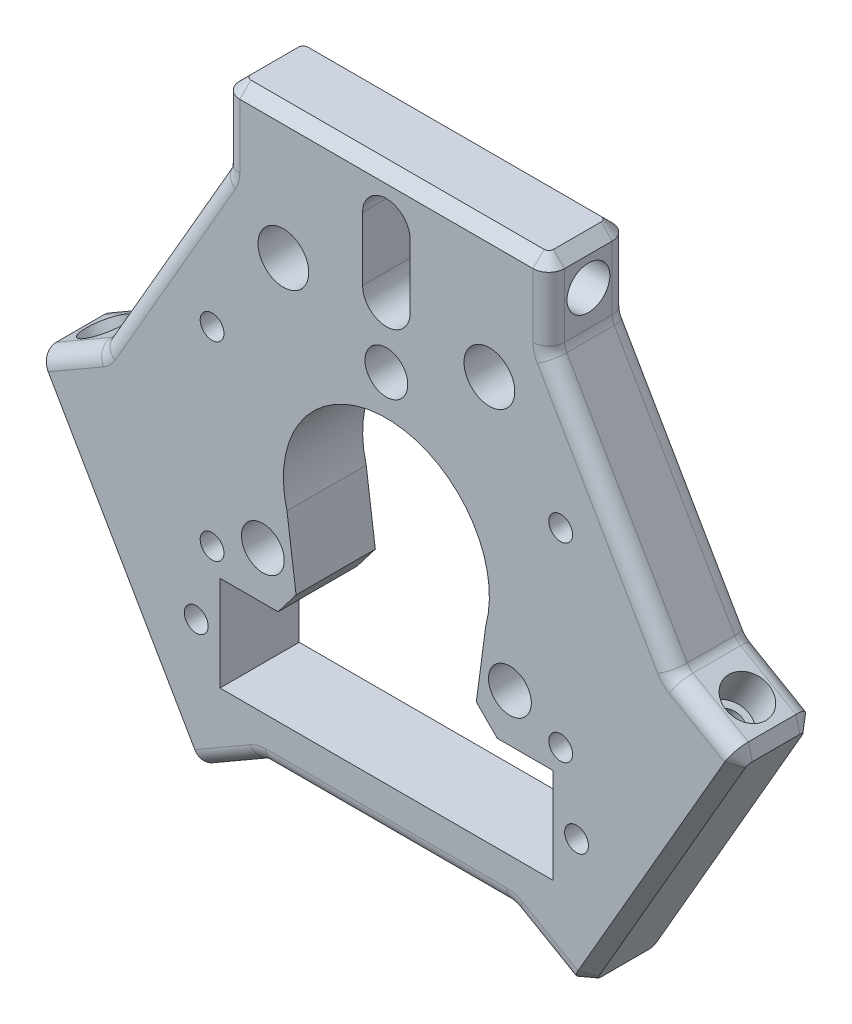
SolidWorks part; units mm, degrees
ref_plane "前基準面" through (0, 0, 0) normal (0, 0, 1) x (1, 0, 0)
ref_plane "上基準面" through (0, 0, 0) normal (0, 1, 0) x (1, 0, 0)
ref_plane "右基準面" through (0, 0, 0) normal (1, 0, 0) x (0, 0, -1)
sketch "草圖1" plane through (0, 0, 0) normal (0, 0, 1) x (1, 0, 0)
  line L0 (0, 0) -> (0, 40) construction
  line L1 (-20.5, 40) -> (20.5, 40)
  line L2 (20.5, 40) -> (20.5, 30)
  line L3 (-20.5, 40) -> (-20.5, 30)
  line L4 (44.891, -2.2465) -> (36.2308, 2.7535)
  line L5 (44.891, -2.2465) -> (24.391, -37.7535)
  line L6 (24.391, -37.7535) -> (15.7308, -32.7535)
  line L7 (-24.391, -37.7535) -> (-15.7308, -32.7535)
  line L8 (-24.391, -37.7535) -> (-44.891, -2.2465)
  line L9 (-44.891, -2.2465) -> (-36.2308, 2.7535)
  line L10 (-36.2308, 2.7535) -> (-20.5, 30)
  line L11 (20.5, 30) -> (36.2308, 2.7535)
  line L12 (15.7308, -32.7535) -> (-15.7308, -32.7535)
  line L13 (0, 0) -> (34.641, -20) construction
  line L14 (0, 0) -> (-34.641, -20) construction
  circle A0 centre (0, 0) radius 13
  point P6 (0, 0)
  point P9 (0, 40)
  point P22 (0, 0)
  point P23 (0, 0)
  dimension "D1" = 26
  dimension "D2" = 40
  dimension "D3" = 20.5
  dimension "D4" = 10
  dimension "D6" = 20.5
  dimension "D7" = 3
  dimension "D8" = 40
  dimension "D9" = 40
  dimension "D10" = 72.7535
  dimension "D5" = 3
extrude "填料-伸長1" add sketch "草圖1" along normal blind 10
ref_plane "平面1" through (0, 4.6791, 12.8558) normal (0, 0.342, 0.9397) x (-1, 0, 0)
sketch "草圖2" plane through (-20.5, 0, 0) normal (-1, 0, 0) x (0, 0, 1)
  circle A0 centre (5, 35) radius 2.7
  dimension "D1" = 5.4
extrude "除料-伸長1" cut sketch "草圖2" against normal blind 5
mirror "鏡射1" about plane through (0, 0, 0) normal (1, 0, 0) of "除料-伸長1"
pattern_circular "環狀複製排列1" count 3 over 360 about axis through (0, 0, 10) along (0, 0, -1) of "除料-伸長1", "鏡射1"
sketch "草圖3" plane through (0, 0, 10) normal (0, 0, -1) x (-1, 0, 0)
  circle A0 centre (0, 18) radius 2.7
  circle A1 centre (15.5885, -9) radius 2.7
  circle A2 centre (-15.5885, -9) radius 2.7
  point P8 (0, 0)
  dimension "D1" = 5.4
  dimension "D3" = 18
  dimension "D2" = 3
extrude "除料-伸長2" cut sketch "草圖3" along normal blind 5
sketch "草圖4" plane through (0, 0, 0) normal (0, 0, -1) x (-1, 0, 0)
  line L0 (0, -32.7535) -> (0, 40) construction
  line L1 (15.7308, -32.7535) -> (-15.7308, -32.7535) construction
  line L2 (-63.2298, 0) -> (49.6692, 0) construction
  line L3 (-20.5, 40) -> (20.5, 40) construction
  circle A1 centre (22, -12) radius 1.5
  circle A2 centre (22, 12) radius 1.5
  circle A3 centre (-22, 12) radius 1.5
  circle A4 centre (-22, -12) radius 1.5
  dimension "D3" = 3
  dimension "D4" = 3
  dimension "D1" = 24
  dimension "D2" = 12
  dimension "D5" = 22
extrude "除料-伸長3" cut sketch "草圖4" against normal through all
sketch "草圖6" plane through (0, 0, 10) normal (0, 0, 1) x (1, 0, 0)
  line L0 (0, 34) -> (0, 26) construction
  line L1 (3, 34) -> (3, 26)
  line L2 (-3, 34) -> (-3, 26)
  arc A0 (3, 34) -> (-3, 34) centre (0, 34) ccw
  arc A1 (-3, 26) -> (3, 26) centre (0, 26) ccw
  point P4 (0, 30)
  dimension "D1" = 8
  dimension "D2" = 6
  dimension "D3" = 26
extrude "除料-伸長5" cut sketch "草圖6" against normal through all
sketch "草圖7" plane through (0, 0, 10) normal (0, 0, 1) x (1, 0, 0)
  line L0 (0, 0) -> (0, -32.7535) construction
  line L1 (-15.7308, -32.7535) -> (15.7308, -32.7535) construction
  circle A0 centre (-13, 24) radius 3.2
  circle A1 centre (13, 24) radius 3.2
  dimension "D1" = 6.4
  dimension "D2" = 13
  dimension "D3" = 24
extrude "除料-伸長6" cut sketch "草圖7" against normal blind 8
chamfer "導角2" distance 1.4 angle 45 6 edges at (0, 40, 0) (34.641, -20, 0) (-34.641, -20, 0) (34.641, -20, 10) (0, 40, 10) (-34.641, -20, 10)
fillet "圓角2" radius 2 24 edges at (39.9547, 0.6035, 10) (39.9547, 0.6035, 0) (20.5, 34.3, 10) (20.5, 34.3, 0) (-20.5, 34.3, 10) (-20.5, 34.3, 0) (-39.9547, 0.6035, 10) (-39.9547, 0.6035, 0) (-19.4547, -34.9035, 10) (-19.4547, -34.9035, 0) (19.4547, -34.9035, 10) (19.4547, -34.9035, 0) (36.2308, 2.7535, 5) (28.3654, 16.3768, 10) (20.5, 30, 5) (28.3654, 16.3768, 0) (-20.5, 30, 5) (-28.3654, 16.3768, 10) (-36.2308, 2.7535, 5) (-28.3654, 16.3768, 0) (-15.7308, -32.7535, 5) (0, -32.7535, 10) (15.7308, -32.7535, 5) (0, -32.7535, 0)
chamfer "導角3" distance 1.4 angle 45 18 edges at (20.4768, 40, 8.3035) (20.4768, 40, 1.6965) (20.5, 40, 5) (44.8794, -2.2665, 8.3035) (44.8794, -2.2665, 1.6965) (44.891, -2.2465, 5) (24.4026, -37.7335, 8.3035) (24.4026, -37.7335, 1.6965) (24.391, -37.7535, 5) (-24.4026, -37.7335, 8.3035) (-24.4026, -37.7335, 1.6965) (-24.391, -37.7535, 5) (-44.8794, -2.2665, 8.3035) (-44.8794, -2.2665, 1.6965) (-44.891, -2.2465, 5) (-20.4768, 40, 8.3035) (-20.4768, 40, 1.6965) (-20.5, 40, 5)
sketch "草圖9" plane through (0, 0, 5) normal (0, 0, 1) x (1, 0, 0)
  circle A0 centre (15.5885, -9) radius 1.8
  circle A1 centre (-15.5885, -9) radius 1.8
  circle A2 centre (0, 18) radius 1.8
  point P9 (0, 0)
  dimension "D1" = 3.6
  dimension "D2" = 3
extrude "除料-伸長8" cut sketch "草圖9" against normal through all
sketch "草圖10" plane through (-15.5, 0, 0) normal (-1, 0, 0) x (0, 0, 1)
  circle A0 centre (5, 35) radius 1.8
  dimension "D1" = 3.6
extrude "除料-伸長9" cut sketch "草圖10" against normal blind 10
mirror "鏡射2" about plane through (0, 0, 0) normal (1, 0, 0) of "除料-伸長9"
pattern_circular "環狀複製排列2" count 3 over 360 about axis through (0, 0, 10) along (0, 0, -1) of "鏡射2", "除料-伸長9"
sketch "草圖11" plane through (0, 0, 0) normal (0, 0, -1) x (-1, 0, 0)
  line L1 (-21, -15) -> (21, -15)
  line L2 (-21, -15) -> (-21, -27)
  line L3 (-21, -27) -> (21, -27)
  line L4 (21, -15) -> (21, -27)
  circle A0 centre (24, -21) radius 1.5
  circle A1 centre (-24, -21) radius 1.5
  point P4 (0, -15)
  point P11 (21, -21)
  point P13 (-21, -21)
  dimension "D4" = 3
  dimension "D5" = 3
  dimension "D7" = 3
  dimension "D1" = 42
  dimension "D2" = 12
  dimension "D3" = 15
  dimension "D6" = 3
  dimension "D8" = 48
extrude "除料-伸長10" cut sketch "草圖11" against normal through all
sketch "草圖12" plane through (0, 0, 2) normal (0, 0, 1) x (1, 0, 0)
  circle A0 centre (-13, 24) radius 2.7
  circle A1 centre (13, 24) radius 2.7
  dimension "D1" = 5.4
  dimension "D2" = 5.4
extrude "除料-伸長11" cut sketch "草圖12" against normal through all
sketch "草圖13" plane through (0, 0, 10) normal (0, 0, 1) x (1, 0, 0)
  line L0 (-13, 0) -> (-11, -15)
  line L1 (-21, -15) -> (21, -15) construction
  line L2 (0, 0) -> (0, -15) construction
  line L3 (13, 0) -> (11, -15)
  line L4 (-13, 0) -> (13, 0)
  line L5 (-11, -15) -> (11, -15)
  circle A0 centre (0, 0) radius 13 construction
  dimension "D1" = 11
extrude "除料-伸長12" cut sketch "草圖13" against normal through all
chamfer "導角4" distance 3 angle 45 2 edges at (11, -15, 5) (-11, -15, 5) first distance on face at (16, -15, 5) first distance on face at (-11.7729, -9.2031, 5)
